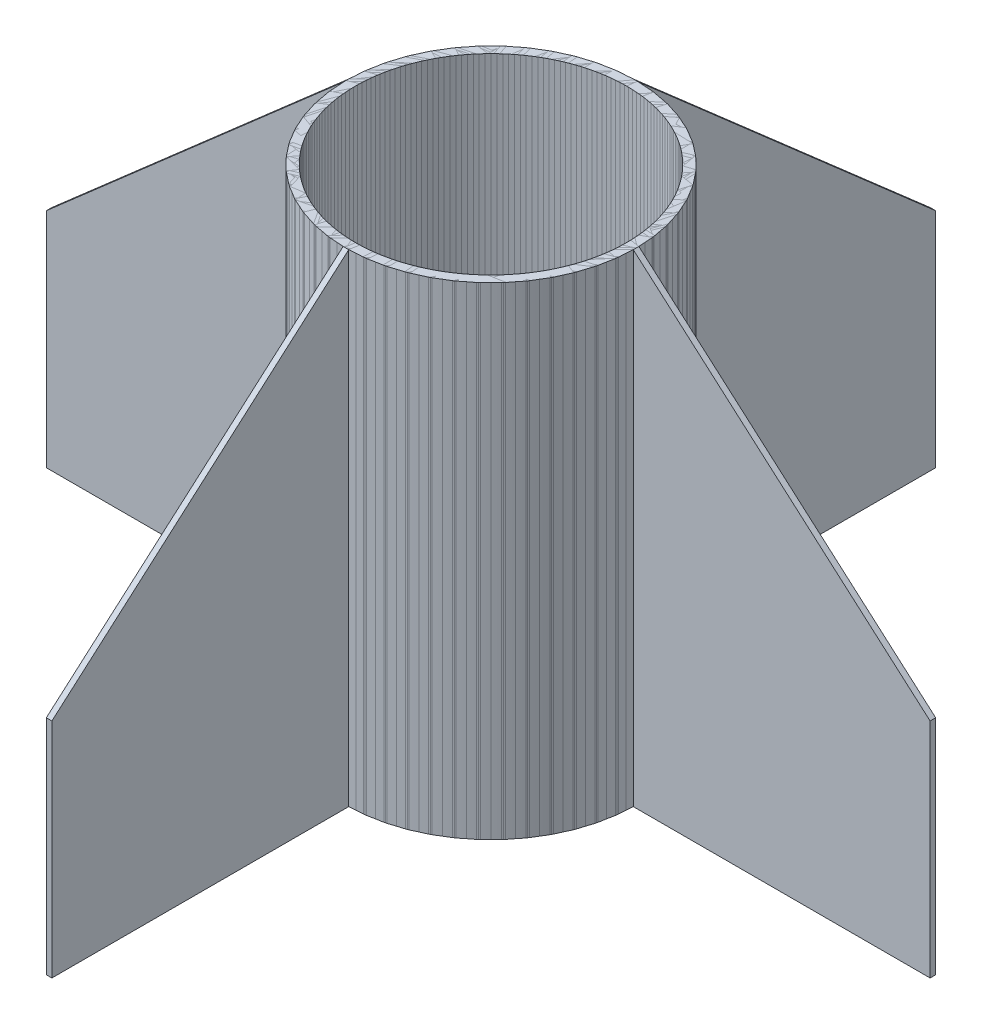
SolidWorks part; units mm, degrees
material "Commercially Pure grade 2 longitudinal (SS)"
ref_plane "Front Plane" through (0, 0, 0) normal (0, 0, 1) x (1, 0, 0)
ref_plane "Top Plane" through (0, 0, 0) normal (0, 1, 0) x (1, 0, 0)
ref_plane "Right Plane" through (0, 0, 0) normal (1, 0, 0) x (0, 0, -1)
sketch "Sketch1" plane through (0, 0, 0) normal (0, 1, 0) x (1, 0, 0)
  circle A0 centre (0, 0) radius 78.2
  circle A1 centre (0, 0) radius 73.2
  dimension "D1" = 156.4
  dimension "D2" = 146.4
extrude "Boss-Extrude1" add sketch "Sketch1" along normal blind 260
sketch "Sketch2" plane through (0, 0, 0) normal (0, 0, 1) x (1, 0, 0)
  line L0 (78.2, 0) -> (78.2, 260) construction
  line L1 (78.2, 0) -> (78.2, 260)
  line L2 (78.2, 0) -> (238.2, 0)
  line L3 (238.2, 0) -> (238.2, 120)
  line L4 (238.2, 120) -> (78.2, 260)
  dimension "D1" = 160
  dimension "D2" = 120
extrude "Boss-Extrude2" add sketch "Sketch2" along normal blind 1.5 and the other way blind 1.5 separate body
sketch "Sketch4" plane through (0, 0, 0) normal (0, 0, 1) x (1, 0, 0)
  line L0 (78.2, 260) -> (78.2, 0) construction
  line L1 (78.2, 260) -> (78.2, 0)
  line L2 (78.2, 260) -> (76.2, 260)
  line L3 (78.2, 260) -> (-78.2, 260) construction
  line L4 (76.2, 260) -> (76.2, 0)
  line L5 (-78.2, 0) -> (78.2, 0) construction
  line L6 (76.2, 0) -> (78.2, 0)
  point P2 (78.2, 130)
  dimension "D1" = 2
extrude "Boss-Extrude3" add sketch "Sketch4" along normal blind 1.5 and the other way blind 1.5
pattern_circular "CirPattern1" count 4 over 360 about axis through (0, 260, 0) along (0, -1, 0) of bodies 103
